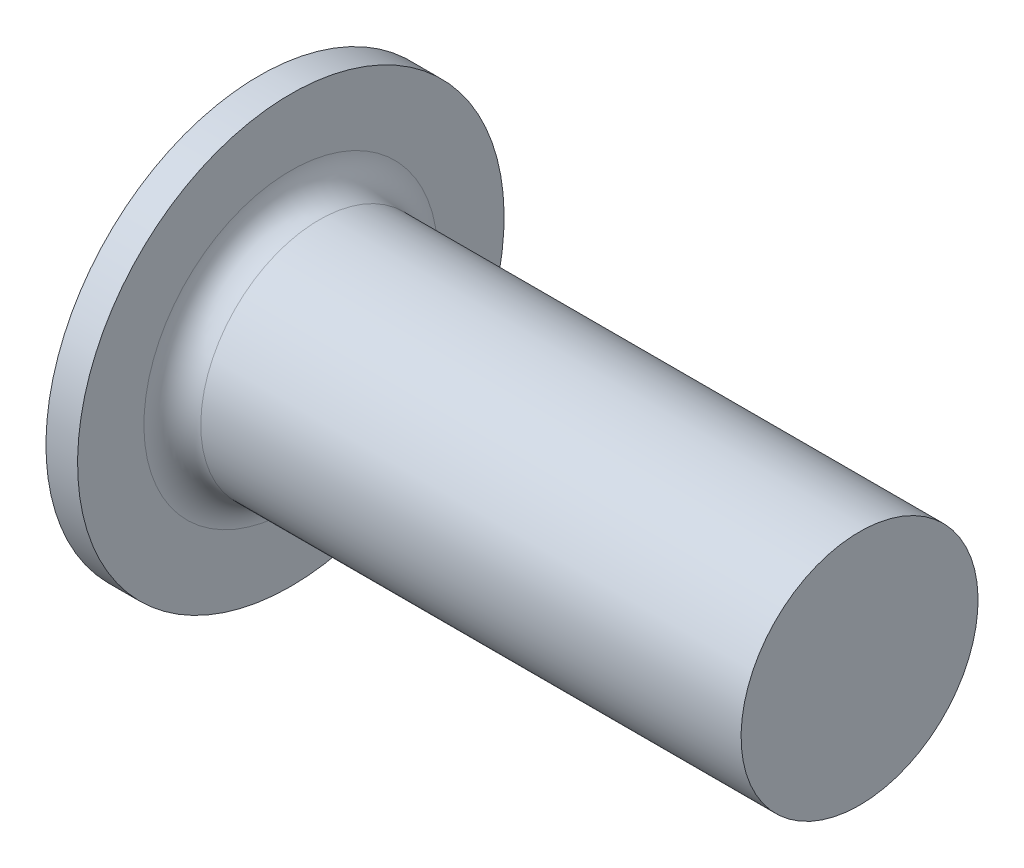
SolidWorks part; units mm, degrees
material "AISI 304"
ref_plane "Front Plane" through (0, 0, 0) normal (0, 0, 1) x (1, 0, 0)
ref_plane "Top Plane" through (0, 0, 0) normal (0, 1, 0) x (1, 0, 0)
ref_plane "Right Plane" through (0, 0, 0) normal (1, 0, 0) x (0, 0, -1)
ref_plane "Plane1" through (-1, 0, 0) normal (1, 0, 0) x (0, 0, -1)
sketch "Sketch1" plane through (0, 0, 0) normal (0, 0, 1) x (1, 0, 0)
  line L0 (-1, 0) -> (12, 0) construction
  line L1 (0, 2.5) -> (12, 2.5)
  line L2 (12, 2.5) -> (12, 0)
  line L3 (12, 0) -> (-1, 0)
  line L4 (-1, 0) -> (-1, 3.9226)
  line L5 (-1, 3.9226) -> (-0.6667, 4.5)
  line L6 (-0.6667, 4.5) -> (0, 4.5)
  line L7 (0, 4.5) -> (0, 2.5)
  dimension "M" = 5
  dimension "L" = 12
  dimension "FIX_1" = 30
  dimension "A" = 9
  dimension "E" = 1
  dimension "KSS_1" = 0.6667
revolve "Revolve1" add sketch "Sketch1" angle 360 about L0
cosmetic thread "Thread1" parameters "ATD"=4.134
chamfer "Chamfer1" [suppressed] distance 0.2 angle 45
sketch "Sketch2" plane through (-1, 0, 0) normal (1, 0, 0) x (0, 0, -1)
  line L0 (0, 1.4) -> (0, -1.4) construction
  line L1 (1.4, 0) -> (-1.4, 0) construction
  line L2 (1.2124, 0.7) -> (-1.2124, -0.7) construction
  line L3 (-1.2124, 0.7) -> (1.2124, -0.7) construction
  line L4 (0.7, 1.2124) -> (-0.7, -1.2124) construction
  line L5 (-0.7, 1.2124) -> (0.7, -1.2124) construction
  circle A0 centre (0, 0) radius 1.4 construction
  circle A1 centre (0, 0) radius 1.025 construction
  arc A2 (0.2688, 1.1983) -> (-0.2688, 1.1983) centre (0, 1.12) ccw
  arc A3 (1.1721, 0.3663) -> (0.9033, 0.832) centre (0.9699, 0.56) ccw
  arc A4 (0.9033, -0.832) -> (1.1721, -0.3663) centre (0.9699, -0.56) ccw
  arc A5 (-0.2688, -1.1983) -> (0.2688, -1.1983) centre (0, -1.12) ccw
  arc A6 (-1.1721, -0.3663) -> (-0.9033, -0.832) centre (-0.9699, -0.56) ccw
  arc A7 (-0.9033, 0.832) -> (-1.1721, 0.3663) centre (-0.9699, 0.56) ccw
  arc A8 (0.2688, 1.1983) -> (0.9033, 0.832) centre (0.7773, 1.3463) ccw
  arc A9 (1.1721, 0.3663) -> (1.1721, -0.3663) centre (1.5545, 0) ccw
  arc A10 (0.9033, -0.832) -> (0.2688, -1.1983) centre (0.7773, -1.3463) ccw
  arc A11 (-0.2688, -1.1983) -> (-0.9033, -0.832) centre (-0.7773, -1.3463) ccw
  arc A12 (-1.1721, -0.3663) -> (-1.1721, 0.3663) centre (-1.5545, 0) ccw
  arc A13 (-0.9033, 0.832) -> (-0.2688, 1.1983) centre (-0.7773, 1.3463) ccw
  dimension "MSM_1" = 2.8
  dimension "MSM_2" = 2.05
  dimension "MSM_3" = 0.28
  dimension "FIX_5" = 30
  dimension "FIX_6" = 30
  dimension "FIX_7" = 60
  dimension "FIX_8" = 60
extrude "Cut-Extrude1" cut sketch "Sketch2" along normal blind 1
fillet "Fillet1" radius 0.6 1 edges at (0, -2.5, 0)
equation "\"KSS_1@Sketch1\"= \"E@Sketch1\" * 2 / 3"
